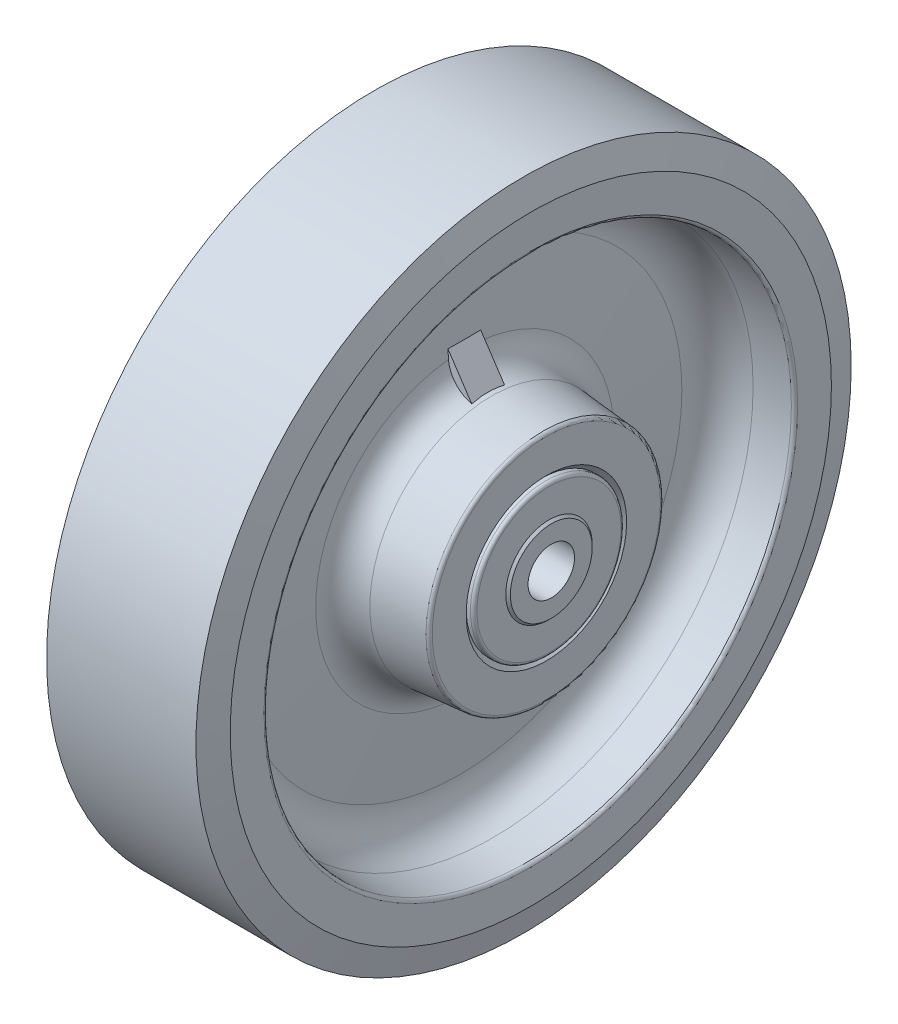
SolidWorks part; units mm, degrees
material "POLIURETANICHE (11671)"
ref_plane "Piano frontale" through (0, 0, 0) normal (0, 0, 1) x (1, 0, 0)
ref_plane "Piano superiore" through (0, 0, 0) normal (0, 1, 0) x (1, 0, 0)
ref_plane "Piano destro" through (0, 0, 0) normal (1, 0, 0) x (0, 0, -1)
other "Centro di massa"
sketch "Schizzo1" plane through (0, 0, 0) normal (0, 0, 1) x (1, 0, 0)
  line L0 (0, 0) -> (-102055.8899, 0) construction
  line L1 (0, 0) -> (0, 102055.8899) construction
  line L2 (22.79, 100) -> (-22.79, 100)
  line L3 (-22.79, 100) -> (-25.0003, 91.751)
  line L4 (-25.0003, 91.751) -> (-25.0003, 81.4393)
  line L5 (-24.0875, 80.4431) -> (-13.3439, 79.5031)
  line L6 (-3.3294, 67.7777) -> (-4.8838, 45.5483)
  line L7 (-13.0775, 37.2104) -> (-28.8372, 35.8316)
  line L8 (-29.75, 34.8354) -> (-29.75, 24.5)
  line L9 (-29.75, 24.5) -> (-28.25, 23)
  line L10 (-28.25, 23) -> (-29.55, 23)
  line L11 (-30.55, 22) -> (-30.55, 13.2)
  line L12 (-30.55, 13.2) -> (-31.25, 12.5)
  line L13 (-31.25, 12.5) -> (-31.25, 7.095)
  line L14 (-31.25, 7.095) -> (-10.65, 7.095)
  line L15 (-10.65, 7.095) -> (-10.65, 10.495)
  line L16 (-10.65, 10.495) -> (10.65, 10.495)
  line L17 (10.65, 7.095) -> (10.65, 10.495)
  line L18 (31.25, 7.095) -> (10.65, 7.095)
  line L19 (31.25, 12.5) -> (31.25, 7.095)
  line L20 (30.55, 13.2) -> (31.25, 12.5)
  line L21 (30.55, 22) -> (30.55, 13.2)
  line L22 (28.25, 23) -> (29.55, 23)
  line L23 (29.75, 24.5) -> (28.25, 23)
  line L24 (29.75, 34.8354) -> (29.75, 24.5)
  line L25 (13.0775, 37.2104) -> (28.8372, 35.8316)
  line L26 (3.3294, 67.7777) -> (4.8838, 45.5483)
  line L27 (24.0875, 80.4431) -> (13.3439, 79.5031)
  line L28 (25.0003, 91.751) -> (25.0003, 81.4393)
  line L29 (22.79, 100) -> (25.0003, 91.751)
  arc A0 (-25.0003, 81.4393) -> (-24.0875, 80.4431) centre (-24.0003, 81.4393) ccw
  arc A1 (-28.8372, 35.8316) -> (-29.75, 34.8354) centre (-28.75, 34.8354) ccw
  arc A2 (-13.3439, 79.5031) -> (-3.3294, 67.7777) centre (-14.3026, 68.545) cw
  arc A3 (-4.8838, 45.5483) -> (-13.0775, 37.2104) centre (-13.8619, 46.1761) cw
  arc A4 (-29.55, 23) -> (-30.55, 22) centre (-29.55, 22) ccw
  arc A5 (29.55, 23) -> (30.55, 22) centre (29.55, 22) cw
  arc A6 (4.8838, 45.5483) -> (13.0775, 37.2104) centre (13.8619, 46.1761) ccw
  arc A7 (13.3439, 79.5031) -> (3.3294, 67.7777) centre (14.3026, 68.545) ccw
  arc A8 (28.8372, 35.8316) -> (29.75, 34.8354) centre (28.75, 34.8354) cw
  arc A9 (25.0003, 81.4393) -> (24.0875, 80.4431) centre (24.0003, 81.4393) cw
  point P6 (30.55, 23)
  point P21 (-2.5753, 78.561)
  point P24 (-5.42, 37.8803)
  point P46 (-30.55, 23)
  point P63 (0, 10.495)
  point P71 (0, 100)
  point P72 (5.42, 37.8803)
  point P73 (2.5753, 78.561)
  dimension "D8" = 1
  dimension "D13" = 1
  dimension "D14" = 11
  dimension "D15" = 9
  dimension "D26" = 1
  dimension "D1" = 22.79
  dimension "D2" = 105
  dimension "D3" = 8.54
  dimension "D4" = 95
  dimension "D5" = 13.19
  dimension "D6" = 100
  dimension "D7" = 4
  dimension "D9" = 95
  dimension "D10" = 40.78
  dimension "D11" = 59.5
  dimension "D12" = 24.33
  dimension "D16" = 75.5
  dimension "D17" = 135
  dimension "D18" = 1.5
  dimension "D19" = 9.8
  dimension "D20" = 135
  dimension "D21" = 14.19
  dimension "D22" = 20.99
  dimension "D23" = 20.6
  dimension "D24" = 0.8
  dimension "D25" = 0.7
revolve "Rivoluzione1" add sketch "Schizzo1" angle 360 about L0
ref_axis "Assi1" through (-154.7401, 0, 0) along (1, 0, 0)
sketch "Schizzo3" plane through (0, 0, 0) normal (0, 0, 1) x (1, 0, 0)
  line L0 (0, 55) -> (-13.3439, 35)
  line L1 (0, 0) -> (0, 1000) construction
  line L2 (0, 50) -> (0, -50) construction
  line L3 (-13.3439, 79.5031) -> (-13.3439, -79.5031) construction
  line L4 (-13.3439, 35) -> (0, 35)
  line L5 (0, 35) -> (0, 55)
  line L6 (-154.7401, 0) -> (152.4338, 0) construction
  dimension "D1" = 20
  dimension "D2" = 35
extrude "Estrusione-Estrusione1" add sketch "Schizzo3" along normal mid plane 10
mirror "Specchia1" about plane through (0, 0, 0) normal (1, 0, 0) of "Estrusione-Estrusione1"
